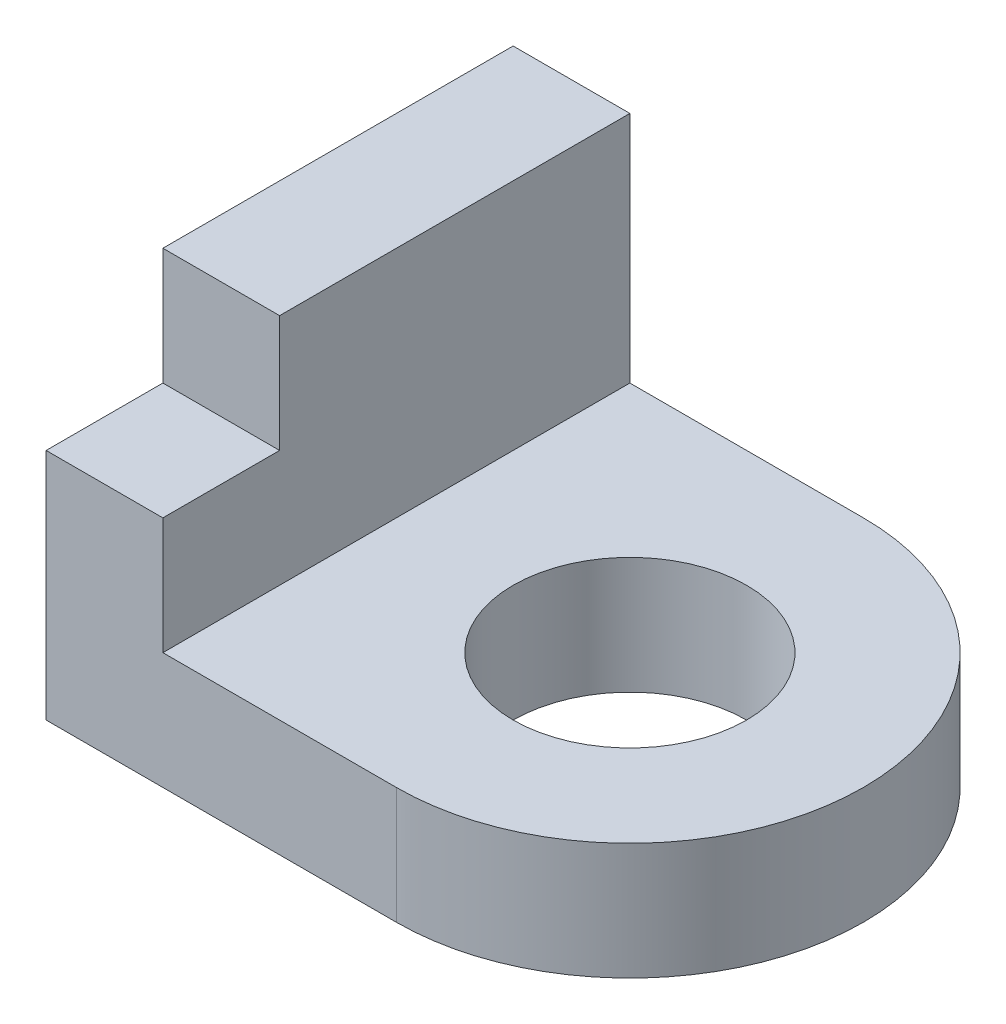
SolidWorks part; units mm, degrees
ref_plane "前基準面" through (0, 0, 0) normal (0, 0, 1) x (1, 0, 0)
ref_plane "上基準面" through (0, 0, 0) normal (0, 1, 0) x (1, 0, 0)
ref_plane "右基準面" through (0, 0, 0) normal (1, 0, 0) x (0, 0, -1)
sketch "草圖1" plane through (0, 0, 0) normal (0, 1, 0) x (1, 0, 0)
  line L1 (0, 10) -> (-15, 10)
  line L3 (0, -10) -> (-15, -10)
  line L4 (-15, 10) -> (-15, -10)
  line L5 (-15, 10) -> (-10, 10)
  line L6 (-15, 10) -> (-15, -5)
  line L7 (-15, -5) -> (-10, -5)
  line L8 (-10, 10) -> (-10, -5)
  line L9 (-15, -10) -> (-10, -10)
  line L10 (-15, -10) -> (-15, -5)
  line L11 (-15, -5) -> (-10, -5)
  line L12 (-10, -10) -> (-10, -5)
  circle A0 centre (0, 0) radius 5
  arc A1 (0, -10) -> (0, 10) centre (0, 0) ccw
  dimension "D1" = 20
  dimension "D2" = 10
  dimension "D4" = 5
  dimension "D5" = 5
extrude "填料-伸長1" add sketch "草圖1" along normal blind 5 contours L3 A1 L1 L8 L12 A0 region at (9.7172, 0, 0)
extrude "填料-伸長2" add sketch "草圖1<3>" along normal blind 10 contours L3 L12 L7 L4 region at (-12.5, 0, 7.5)
sketch "草圖1<3>" plane through (0, 0, 0) normal (0, 1, 0) x (1, 0, 0) same geometry as "草圖1"
extrude "填料-伸長3" add sketch "草圖1<4>" along normal blind 15 contours L8 L1 L4 L7 region at (-12.5, 0, -2.5)
sketch "草圖1<4>" plane through (0, 0, 0) normal (0, 1, 0) x (1, 0, 0) same geometry as "草圖1"
scale "縮放比例1" scale about centroid uniform scaling yes scale factor 0.2
